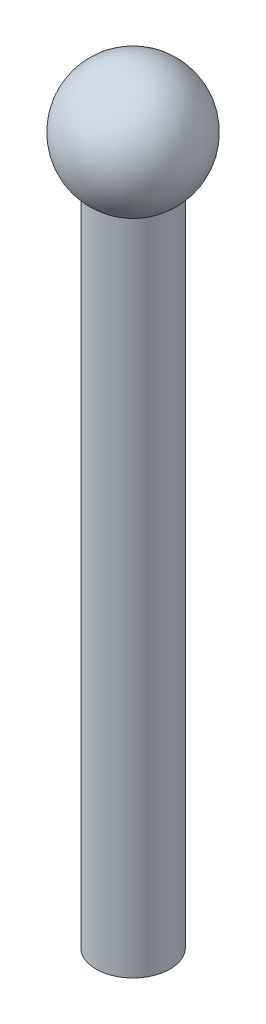
SolidWorks part; units mm, degrees
ref_plane "Front Plane" through (0, 0, 0) normal (0, 0, 1) x (1, 0, 0)
ref_plane "Top Plane" through (0, 0, 0) normal (0, 1, 0) x (1, 0, 0)
ref_plane "Right Plane" through (0, 0, 0) normal (1, 0, 0) x (0, 0, -1)
sketch "Sketch1" plane through (0, 0, 0) normal (0, 1, 0) x (1, 0, 0)
  circle A0 centre (0, 0) radius 6.75
  dimension "D1" = 13.5
extrude "Boss-Extrude1" add sketch "Sketch1" along normal blind 120
dome "Dome1" faces to dome 1 distance 20 reverse direction no elliptical dome no face at (0, 120, 6.75) parameters "D1"=20
